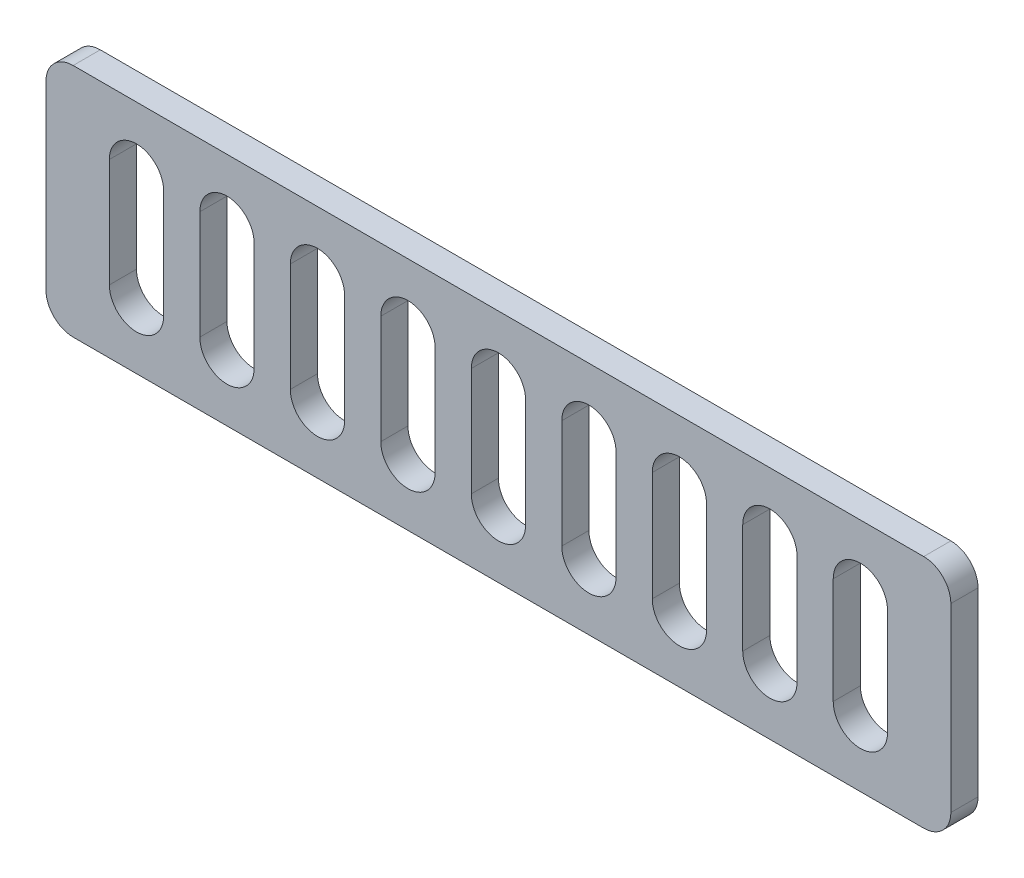
SolidWorks part; units mm, degrees
ref_plane "Front Plane" through (0, 0, 0) normal (0, 0, 1) x (1, 0, 0)
ref_plane "Top Plane" through (0, 0, 0) normal (0, 1, 0) x (1, 0, 0)
ref_plane "Right Plane" through (0, 0, 0) normal (1, 0, 0) x (0, 0, -1)
sketch "Sketch1" plane through (0, 0, 0) normal (0, 0, 1) x (1, 0, 0)
  line L0 (-69.4989, -88.401) -> (-69.4989, -100.401) construction
  line L1 (-66.4989, -88.401) -> (-66.4989, -100.401)
  line L2 (-72.4989, -88.401) -> (-72.4989, -100.401)
  line L3 (-59.4989, -88.401) -> (-59.4989, -100.401) construction
  line L4 (-119.4989, -107.401) -> (-19.4989, -107.401)
  line L5 (-19.4989, -81.401) -> (-19.4989, -107.401)
  line L6 (-119.4989, -81.401) -> (-19.4989, -81.401)
  line L7 (-119.4989, -81.401) -> (-119.4989, -107.401)
  line L8 (-109.4989, -88.401) -> (-109.4989, -100.401) construction
  line L9 (-106.4989, -88.401) -> (-106.4989, -100.401)
  line L10 (-112.4989, -88.401) -> (-112.4989, -100.401)
  line L11 (-99.4989, -88.401) -> (-99.4989, -100.401) construction
  line L12 (-96.4989, -88.401) -> (-96.4989, -100.401)
  line L13 (-102.4989, -88.401) -> (-102.4989, -100.401)
  line L14 (-49.4989, -88.3556) -> (-49.4989, -100.4465) construction
  line L17 (-89.4989, -88.401) -> (-89.4989, -100.401) construction
  line L18 (-86.4989, -88.401) -> (-86.4989, -100.401)
  line L19 (-92.4989, -88.401) -> (-92.4989, -100.401)
  line L20 (-79.4989, -88.401) -> (-79.4989, -100.401) construction
  line L21 (-76.4989, -88.401) -> (-76.4989, -100.401)
  line L22 (-82.4989, -88.401) -> (-82.4989, -100.401)
  line L23 (-56.4989, -88.401) -> (-56.4989, -100.401)
  line L26 (-62.4989, -88.401) -> (-62.4989, -100.401)
  line L27 (-13.6484, -94.401) -> (-124.7235, -94.401) construction
  line L28 (-46.4989, -88.3556) -> (-46.4989, -100.4465)
  line L29 (-52.4989, -88.3556) -> (-52.4989, -100.4465)
  line L30 (-39.4989, -88.3465) -> (-39.4989, -100.4555) construction
  line L31 (-36.4989, -88.3465) -> (-36.4989, -100.4555)
  line L32 (-42.4989, -88.3465) -> (-42.4989, -100.4555)
  line L33 (-29.4989, -88.5311) -> (-29.4989, -100.271) construction
  line L34 (-26.4989, -88.5311) -> (-26.4989, -100.271)
  line L35 (-32.4989, -88.5311) -> (-32.4989, -100.271)
  arc A0 (-106.4989, -88.401) -> (-112.4989, -88.401) centre (-109.4989, -88.401) ccw
  arc A1 (-112.4989, -100.401) -> (-106.4989, -100.401) centre (-109.4989, -100.401) ccw
  arc A2 (-96.4989, -88.401) -> (-102.4989, -88.401) centre (-99.4989, -88.401) ccw
  arc A3 (-102.4989, -100.401) -> (-96.4989, -100.401) centre (-99.4989, -100.401) ccw
  arc A6 (-86.4989, -88.401) -> (-92.4989, -88.401) centre (-89.4989, -88.401) ccw
  arc A7 (-92.4989, -100.401) -> (-86.4989, -100.401) centre (-89.4989, -100.401) ccw
  arc A8 (-76.4989, -88.401) -> (-82.4989, -88.401) centre (-79.4989, -88.401) ccw
  arc A9 (-82.4989, -100.401) -> (-76.4989, -100.401) centre (-79.4989, -100.401) ccw
  arc A12 (-66.4989, -88.401) -> (-72.4989, -88.401) centre (-69.4989, -88.401) ccw
  arc A13 (-72.4989, -100.401) -> (-66.4989, -100.401) centre (-69.4989, -100.401) ccw
  arc A14 (-56.4989, -88.401) -> (-62.4989, -88.401) centre (-59.4989, -88.401) ccw
  arc A15 (-62.4989, -100.401) -> (-56.4989, -100.401) centre (-59.4989, -100.401) ccw
  arc A16 (-46.4989, -88.3556) -> (-52.4989, -88.3556) centre (-49.4989, -88.3556) ccw
  arc A17 (-52.4989, -100.4465) -> (-46.4989, -100.4465) centre (-49.4989, -100.4465) ccw
  arc A18 (-36.4989, -88.3465) -> (-42.4989, -88.3465) centre (-39.4989, -88.3465) ccw
  arc A19 (-42.4989, -100.4555) -> (-36.4989, -100.4555) centre (-39.4989, -100.4555) ccw
  arc A20 (-26.4989, -88.5311) -> (-32.4989, -88.5311) centre (-29.4989, -88.5311) ccw
  arc A21 (-32.4989, -100.271) -> (-26.4989, -100.271) centre (-29.4989, -100.271) ccw
  point P6 (-109.4989, -94.401)
  point P13 (-99.4989, -94.401)
  point P20 (-49.4989, -94.401)
  point P27 (-89.4989, -94.401)
  point P34 (-79.4989, -94.401)
  point P41 (-69.4989, -94.401)
  point P48 (-59.4989, -94.401)
  point P55 (0, 0)
  point P56 (0, 0)
  point P57 (0, 0)
  point P58 (0, 0)
  point P59 (0, 0)
  point P60 (0, 0)
  point P63 (-39.4989, -94.401)
  point P70 (-29.4989, -94.401)
  point P75 (0, 0)
  point P76 (0, 0)
  point P77 (0, 0)
  dimension "D10" = 3
  dimension "D1" = 13
  dimension "D2" = 26
  dimension "D3" = 12
  dimension "D4" = 10
  dimension "D5" = 10
  dimension "D6" = 10
  dimension "D7" = 10
  dimension "D8" = 10
  dimension "D9" = 10
  dimension "D11" = 100
  dimension "D12" = 10
  dimension "D13" = 10
  dimension "D14" = 10
extrude "Boss-Extrude1" add sketch "Sketch1" against normal blind 3
fillet "Fillet1" radius 3 4 edges at (-119.4989, -107.401, -1.5) (-19.4989, -107.401, -1.5) (-19.4989, -81.401, -1.5) (-119.4989, -81.401, -1.5)
